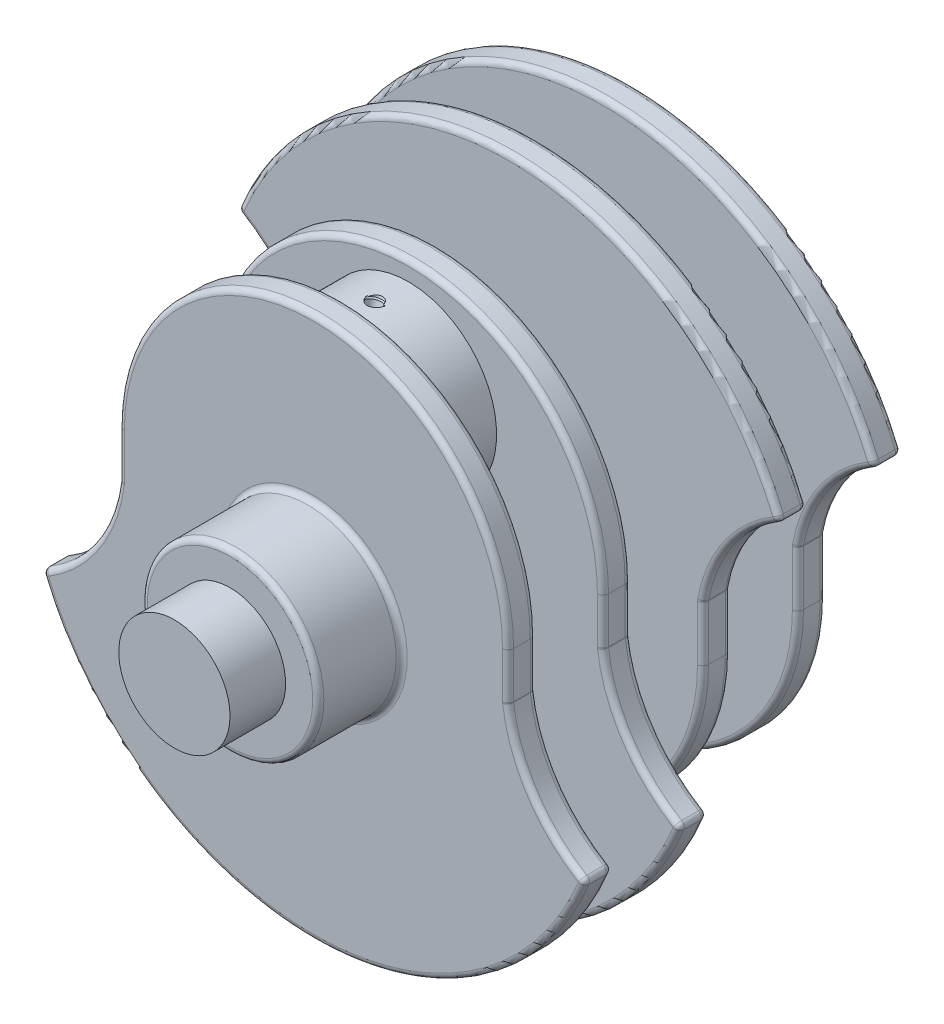
SolidWorks part; units mm, degrees
material "AISI 4340 Steel, normalized"
ref_plane "Front Plane" through (0, 0, 0) normal (0, 0, 1) x (1, 0, 0)
ref_plane "Top Plane" through (0, 0, 0) normal (0, 1, 0) x (1, 0, 0)
ref_plane "Right Plane" through (0, 0, 0) normal (1, 0, 0) x (0, 0, -1)
sketch "Sketch1" plane through (0, 0, 0) normal (0, 0, 1) x (1, 0, 0)
  circle A0 centre (0, 0) radius 31.75
  dimension "D1" = 31.75
extrude "Boss-Extrude1" add sketch "Sketch1" along normal blind 30
sketch "Sketch8" plane through (0, 0, 0) normal (0, 0, -1) x (-1, 0, 0)
  line L0 (-70, 20) -> (-70, 3.36)
  line L1 (70, 20) -> (70, 3.36)
  arc A0 (70, 20) -> (-70, 20) centre (0, 20) ccw
  arc A5 (-97.7839, -38.2532) -> (97.7839, -38.2532) centre (0, 0) ccw
  arc A6 (-70, 3.36) -> (-97.7839, -38.2532) centre (-125, 10) cw
  arc A7 (70, 3.36) -> (97.7839, -38.2532) centre (125, 10) ccw
  dimension "D1" = 70
  dimension "D2" = 105
  dimension "D3" = 20
  dimension "D5" = 10
  dimension "D6" = 125
extrude "Boss-Extrude5" add sketch "Sketch8" along normal blind 10
sketch "Sketch2" plane through (0, 0, 30) normal (0, 0, 1) x (1, 0, 0)
  circle A0 centre (0, 0) radius 20
  dimension "D1" = 20
extrude "Boss-Extrude2" add sketch "Sketch2" along normal blind 20
sketch "Sketch9" plane through (0, 0, -10) normal (0, 0, -1) x (-1, 0, 0)
  circle A0 centre (0, 51.5) radius 31.75
  dimension "D2" = 31.75
  dimension "D1" = 51.5
extrude "Boss-Extrude6" add sketch "Sketch9" along normal blind 24.13
ref_plane "Plane4" through (0, 0, -70.13) normal (0, 0, -1) x (-1, 0, 0)
sketch "Sketch10" plane through (0, 0, -34.13) normal (0, 0, -1) x (-1, 0, 0)
  line L0 (-70, -20) -> (-70, 0)
  line L1 (70, -20) -> (70, 0)
  arc A0 (-70, -20) -> (70, -20) centre (0, -20) ccw
  arc A1 (-70, 0) -> (-97.598, 38.7251) centre (-125, -10) ccw
  arc A2 (70, 0) -> (97.598, 38.7251) centre (125, -10) cw
  arc A3 (-97.598, 38.7251) -> (97.598, 38.7251) centre (0, 0) cw
  dimension "D1" = 70
  dimension "D3" = 105
  dimension "D2" = 20
  dimension "D4" = 125
  dimension "D5" = 10
extrude "Boss-Extrude7" add sketch "Sketch10" along normal blind 10 from surface starting at plane "Plane4"
ref_plane "Plane3" through (0, 0, -104.26) normal (0, 0, -1) x (-1, 0, 0)
sketch "Sketch12" plane through (0, 0, -104.26) normal (0, 0, -1) x (-1, 0, 0)
  line L2 (70, -20) -> (70, 0)
  line L3 (70, -20) -> (70, 0)
  line L4 (-70, 0) -> (-70, -20)
  line L5 (-70, 0) -> (-70, -20)
  arc A12 (-70, -20) -> (70, -20) centre (0, -20) ccw
  arc A13 (97.598, 38.7251) -> (70, 0) centre (125, -10) ccw
  arc A14 (97.598, 38.7251) -> (-97.598, 38.7251) centre (0, 0) ccw
  arc A15 (-70, 0) -> (-97.598, 38.7251) centre (-125, -10) ccw
  arc A16 (-70, -20) -> (70, -20) centre (0, -20) ccw
  arc A17 (97.598, 38.7251) -> (70, 0) centre (125, -10) ccw
  arc A18 (97.598, 38.7251) -> (-97.598, 38.7251) centre (0, 0) ccw
  arc A19 (-70, 0) -> (-97.598, 38.7251) centre (-125, -10) ccw
  dimension "D1" = 0
extrude "Boss-Extrude8" add sketch "Sketch12" along normal blind 10
sketch "Sketch14" plane through (0, 0, -80.13) normal (0, 0, -1) x (-1, 0, 0)
  circle A0 centre (0, -51.5) radius 31.75
  dimension "D2" = 31.75
  dimension "D1" = 51.5
extrude "Boss-Extrude9" add sketch "Sketch14" along normal up to next
sketch "Sketch15" plane through (0, 0, -114.26) normal (0, 0, -1) x (-1, 0, 0)
  circle A1 centre (0, 0) radius 31.75
  circle A2 centre (0, 0) radius 31.75
  dimension "D1" = 0
extrude "Boss-Extrude10" add sketch "Sketch15" along normal blind 30
sketch "Sketch16" plane through (0, 0, -144.26) normal (0, 0, -1) x (-1, 0, 0)
  circle A1 centre (0, 0) radius 20
  circle A2 centre (0, 0) radius 20
  dimension "D1" = 0
extrude "Boss-Extrude11" add sketch "Sketch16" along normal blind 20
sketch "Sketch18" plane through (0, 0, -34.13) normal (0, 0, -1) x (-1, 0, 0)
  line L2 (-70, 20) -> (-70, 3.36)
  line L3 (-70, 20) -> (-70, 3.36)
  line L4 (70, 3.36) -> (70, 20)
  line L5 (70, 3.36) -> (70, 20)
  arc A4 (70, 20) -> (-70, 20) centre (0, 20) ccw
  arc A5 (-97.7839, -38.2532) -> (-70, 3.36) centre (-125, 10) ccw
  arc A6 (-97.7839, -38.2532) -> (97.7839, -38.2532) centre (0, 0) ccw
  arc A7 (70, 3.36) -> (97.7839, -38.2532) centre (125, 10) ccw
  arc A8 (70, 20) -> (-70, 20) centre (0, 20) ccw
  arc A9 (-97.7839, -38.2532) -> (-70, 3.36) centre (-125, 10) ccw
  arc A10 (-97.7839, -38.2532) -> (97.7839, -38.2532) centre (0, 0) ccw
  arc A11 (70, 3.36) -> (97.7839, -38.2532) centre (125, 10) ccw
  dimension "D1" = 0
extrude "Boss-Extrude12" add sketch "Sketch18" along normal blind 10
sketch "Sketch19" plane through (0, 0, -44.13) normal (0, 0, -1) x (-1, 0, 0)
  circle A1 centre (0, 0) radius 31.75
  circle A2 centre (0, 0) radius 31.75
  dimension "D1" = 0
extrude "Boss-Extrude13" add sketch "Sketch19" along normal up to next
fillet "Fillet1" radius 2 32 edges at (0, -105, -34.13) (-78.9263, -20.762, -34.13) (-70, 11.68, -34.13) (70, 11.68, -34.13) (78.9263, -20.762, -34.13) (0, -105, -44.13) (-78.9263, -20.762, -44.13) (-70, 11.68, -44.13) (0, 90, -44.13) (70, 11.68, -44.13) (78.9263, -20.762, -44.13) (97.7839, -38.2532, -39.13) (70, 3.36, -39.13) (-70, 3.36, -39.13) (-97.7839, -38.2532, -39.13) (0, 90, -34.13) (70, 11.68, 0) (78.9263, -20.762, 0) (0, -105, 0) (-78.9263, -20.762, 0) (-70, 11.68, 0) (0, 90, -10) (70, 11.68, -10) (78.9263, -20.762, -10) (0, -105, -10) (-78.9263, -20.762, -10) (-70, 11.68, -10) (-70, 3.36, -5) (-97.7839, -38.2532, -5) (97.7839, -38.2532, -5) (70, 3.36, -5) (0, 90, 0)
fillet "Fillet2" radius 2 16 edges at (0, 105, -104.26) (79.4761, 22.4433, -104.26) (70, -10, -104.26) (0, -90, -104.26) (-70, -10, -104.26) (-79.4761, 22.4433, -104.26) (79.4761, 22.4433, -114.26) (70, -10, -114.26) (0, -90, -114.26) (-70, -10, -114.26) (-79.4761, 22.4433, -114.26) (-97.598, 38.7251, -109.26) (-70, 0, -109.26) (70, 0, -109.26) (97.598, 38.7251, -109.26) (0, 105, -114.26)
fillet "Fillet3" radius 2 16 edges at (70, -10, -70.13) (79.4761, 22.4433, -70.13) (0, 105, -70.13) (-79.4761, 22.4433, -70.13) (-70, -10, -70.13) (0, -90, -70.13) (70, -10, -80.13) (79.4761, 22.4433, -80.13) (-79.4761, 22.4433, -80.13) (-70, -10, -80.13) (0, -90, -80.13) (70, 0, -75.13) (97.598, 38.7251, -75.13) (-97.598, 38.7251, -75.13) (-70, 0, -75.13) (0, 105, -80.13)
fillet "Fillet5" radius 2 2 edges at (31.75, 0, 30) (31.75, 0, 0)
fillet "Fillet6" radius 2 2 edges at (-31.75, 0, -114.26) (-31.75, 0, -144.26)
fillet "Fillet9" radius 2 1 edges at (-31.75, -51.5, -104.26)
ref_plane "Plane5" through (0, 31.75, 0) normal (0, 1, 0) x (1, 0, 0)
sketch "Sketch20" plane through (0, 0, 0) normal (1, 0, 0) x (0, 0, -1)
  line L1 (80.13, -83.25) -> (80.13, -19.75)
  line L2 (80.13, -83.25) -> (80.13, -19.75)
  dimension "D1" = 0
ref_plane "Plane6" through (0, -83.25, 0) normal (0, 1, 0) x (1, 0, 0)
sketch "Sketch21" plane through (0, 31.75, 0) normal (0, 1, 0) x (1, 0, 0)
  line L2 (-31.75, 142.26) -> (31.75, 142.26) construction
  line L3 (-31.75, 142.26) -> (-31.75, 116.26) construction
  line L4 (-31.75, 116.26) -> (31.75, 116.26) construction
  line L5 (31.75, 142.26) -> (31.75, 116.26) construction
  circle A0 centre (0, 129.26) radius 2.5
  point P8 (0, 0)
  point P9 (0, 0)
  point P10 (0, 142.26)
  point P11 (31.75, 129.26)
  point P12 (-31.75, 142.26)
  dimension "D1" = 5
sketch "Sketch22" plane through (0, -83.25, 0) normal (0, 1, 0) x (1, 0, 0)
  line L1 (-31.75, 102.26) -> (31.75, 102.26) construction
  line L2 (-31.75, 102.26) -> (-31.75, 80.13) construction
  line L3 (-31.75, 80.13) -> (31.75, 80.13) construction
  line L4 (31.75, 102.26) -> (31.75, 80.13) construction
  line L5 (-31.75, 102.26) -> (31.75, 80.13) construction
  line L6 (-31.75, 80.13) -> (31.75, 102.26) construction
  circle A0 centre (0, 91.195) radius 2.5
  point P4 (0, 91.195)
  dimension "D1" = 5
sketch "Sketch23" plane through (0, 0, 0) normal (1, 0, 0) x (0, 0, -1)
  line L0 (129.26, 31.75) -> (91.195, -83.25) construction
  line L1 (131.76, 31.75) -> (126.76, 31.75) construction
  point P5 (92.195, -83.25)
  point P6 (92.195, -83.25)
  point P7 (129.26, 31.75)
ref_plane "Plane7" through (0, 31.75, -129.26) normal (0, -0.9493, 0.3142) x (-1, 0, 0)
sketch "Sketch25" plane through (0, 31.75, -129.26) normal (0, -0.9493, 0.3142) x (-1, 0, 0)
  circle A0 centre (0, 0) radius 2.5
  point P0 (0, 0)
  dimension "D1" = 5
hole_wizard "#4 (0.209) Diameter Hole1" positions "Sketch25" profile "Sketch26" hole size "#4" standard "ANSI Inch" end condition through all
sketch "Sketch26" plane through (0, 31.75, -129.26) normal (1, 0, 0) x (0, 0.3142, 0.9493)
  line L0 (0, 0) -> (0, 186.1525)
  line L1 (0, 186.1525) -> (2.6543, 186.1525)
  line L2 (2.6543, 186.1525) -> (2.6543, 0.635)
  line L3 (2.6543, 0.635) -> (3.2893, 0)
  line L5 (3.2893, 0) -> (0, 0)
  line L6 (-2.6543, 0.635) -> (-3.2893, 0) construction
  line L11 (0, -6.35) -> (0, 107.95) construction
  dimension "Thru Hole Dia." = 5.3086
  dimension "Thru Hole Depth" = 186.1525
  dimension "Near C'Sink Dia." = 6.5786
  dimension "Near C'Sink Angle" = 90
sketch "Sketch27" plane through (0, 0, 0) normal (0, 0, 1) x (1, 0, 0)
  line L0 (0, 83.25) -> (0, -31.75) construction
  circle A1 centre (0, 51.5) radius 31.75
  circle A2 centre (0, 51.5) radius 31.75 construction
  circle A3 centre (0, 0) radius 31.75
  circle A4 centre (0, 0) radius 31.75 construction
  dimension "D1" = 0
  dimension "D2" = 0
ref_plane "Plane8" through (0, 83.25, 0) normal (0, -1, 0) x (-1, 0, 0)
ref_plane "Plane9" through (0, -31.75, 0) normal (0, -1, 0) x (-1, 0, 0)
sketch "Sketch28" plane through (0, -31.75, 0) normal (0, -1, 0) x (-1, 0, 0)
  line L1 (-31.75, -2) -> (31.75, -2) construction
  line L2 (-31.75, -2) -> (-31.75, -28) construction
  line L3 (-31.75, -28) -> (31.75, -28) construction
  line L4 (31.75, -2) -> (31.75, -28) construction
  line L5 (-31.75, -2) -> (31.75, -28) construction
  line L6 (-31.75, -28) -> (31.75, -2) construction
  circle A0 centre (0, -15) radius 2.5
  point P4 (0, -15)
  dimension "D1" = 5
sketch "Sketch29" plane through (0, 83.25, 0) normal (0, -1, 0) x (-1, 0, 0)
  line L1 (31.75, 34.13) -> (-31.75, 34.13) construction
  line L2 (31.75, 34.13) -> (31.75, 10) construction
  line L3 (31.75, 10) -> (-31.75, 10) construction
  line L4 (-31.75, 34.13) -> (-31.75, 10) construction
  line L5 (31.75, 34.13) -> (-31.75, 10) construction
  line L6 (31.75, 10) -> (-31.75, 34.13) construction
  circle A0 centre (0, 22.065) radius 2.5
  point P4 (0, 22.065)
  dimension "D1" = 5
sketch "Sketch31" plane through (0, 0, 0) normal (1, 0, 0) x (0, 0, -1)
  line L0 (22.065, 83.25) -> (-15, -31.75) construction
ref_plane "Plane10" through (0, 83.25, -22.065) normal (0, -0.9518, 0.3068) x (-1, 0, 0)
hole_wizard "#4 (0.209) Diameter Hole2" positions "Sketch34" profile "Sketch35" hole size "#4" standard "ANSI Inch" end condition through all
sketch "Sketch34" plane through (0, 83.25, -22.065) normal (0, -0.9518, 0.3068) x (-1, 0, 0)
  point P0 (0, 0)
sketch "Sketch35" plane through (0, 83.25, -22.065) normal (1, 0, 0) x (0, 0.3068, 0.9518)
  line L0 (0, 0) -> (0, 201.2806)
  line L1 (0, 201.2806) -> (2.6543, 201.2806)
  line L2 (2.6543, 201.2806) -> (2.6543, 0.635)
  line L3 (2.6543, 0.635) -> (3.2893, 0)
  line L5 (3.2893, 0) -> (0, 0)
  line L6 (-2.6543, 0.635) -> (-3.2893, 0) construction
  line L11 (0, -6.35) -> (0, 107.95) construction
  dimension "Thru Hole Dia." = 5.3086
  dimension "Thru Hole Depth" = 201.2806
  dimension "Near C'Sink Dia." = 6.5786
  dimension "Near C'Sink Angle" = 90
ref_plane "Plane11" through (0, -31.75, 15) normal (0, -0.9518, 0.3068) x (-1, 0, 0)
hole_wizard "#4 (0.209) Diameter Hole3" positions "Sketch37" profile "Sketch38" hole size "#4" standard "ANSI Inch" end condition through all
sketch "Sketch37" plane through (0, -31.75, 15) normal (0, -0.9518, 0.3068) x (-1, 0, 0)
  point P0 (0, 0)
sketch "Sketch38" plane through (0, -31.75, 15) normal (1, 0, 0) x (0, -0.3068, -0.9518)
  line L0 (0, 0) -> (0, 185.1473)
  line L1 (0, 185.1473) -> (2.6543, 185.1473)
  line L2 (2.6543, 185.1473) -> (2.6543, 0.635)
  line L3 (2.6543, 0.635) -> (3.2893, 0)
  line L5 (3.2893, 0) -> (0, 0)
  line L6 (-2.6543, 0.635) -> (-3.2893, 0) construction
  line L11 (0, -6.35) -> (0, 107.95) construction
  dimension "Thru Hole Dia." = 5.3086
  dimension "Thru Hole Depth" = 185.1473
  dimension "Near C'Sink Dia." = 6.5786
  dimension "Near C'Sink Angle" = 90
ref_plane "Plane12" through (0, -83.25, -91.195) normal (0, -0.9493, 0.3142) x (-1, 0, 0)
hole_wizard "#4 (0.209) Diameter Hole4" positions "Sketch39" profile "Sketch40" hole size "#4" standard "ANSI Inch" end condition through all
sketch "Sketch39" plane through (0, -83.25, -91.195) normal (0, -0.9493, 0.3142) x (-1, 0, 0)
  point P0 (0, 0)
sketch "Sketch40" plane through (0, -83.25, -91.195) normal (1, 0, 0) x (0, -0.3142, -0.9493)
  line L0 (0, 0) -> (0, 201.6738)
  line L1 (0, 201.6738) -> (2.6543, 201.6738)
  line L2 (2.6543, 201.6738) -> (2.6543, 0.635)
  line L3 (2.6543, 0.635) -> (3.2893, 0)
  line L5 (3.2893, 0) -> (0, 0)
  line L6 (-2.6543, 0.635) -> (-3.2893, 0) construction
  line L11 (0, -6.35) -> (0, 107.95) construction
  dimension "Thru Hole Dia." = 5.3086
  dimension "Thru Hole Depth" = 201.6738
  dimension "Near C'Sink Dia." = 6.5786
  dimension "Near C'Sink Angle" = 90
equation "\"Crank Radius\"= 51.5mm"
equation "\"D1@Sketch9\"=\"Crank Radius\""
equation "\"D1@Sketch14\"=\"Crank Radius\""
equation "\"Journal Radius\"= 31.75mm"
equation "\"D1@Sketch1\"=\"Journal Radius\""
equation "\"D2@Sketch9\"=\"Journal Radius\""
equation "\"D2@Sketch14\"=\"Journal Radius\""
equation "\"Lobe Thickness\"= 10mm"
equation "\"D1@Boss-Extrude5\"=\"Lobe Thickness\""
equation "\"D1@Boss-Extrude7\"=\"Lobe Thickness\""
equation "\"D1@Boss-Extrude8\"=\"Lobe Thickness\""
equation "\"D1@Boss-Extrude12\"=\"Lobe Thickness\""
